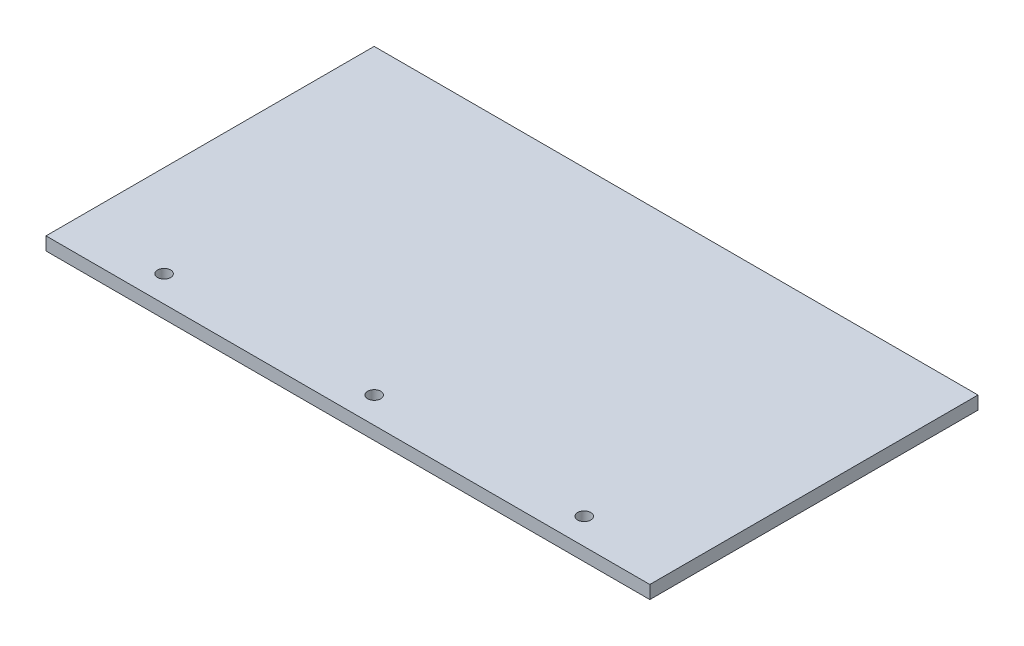
SolidWorks part; units mm, degrees
ref_plane "Front Plane" through (0, 0, 0) normal (0, 0, 1) x (1, 0, 0)
ref_plane "Top Plane" through (0, 0, 0) normal (0, 1, 0) x (1, 0, 0)
ref_plane "Right Plane" through (0, 0, 0) normal (1, 0, 0) x (0, 0, -1)
sketch "Sketch1" plane through (0, 0, 0) normal (0, 1, 0) x (1, 0, 0)
  line L1 (0, 0) -> (292.1, 0)
  line L2 (0, 0) -> (0, 158.75)
  line L3 (0, 158.75) -> (292.1, 158.75)
  line L4 (292.1, 0) -> (292.1, 158.75)
  dimension "D1" = 292.1
  dimension "D2" = 158.75
extrude "Boss-Extrude1" add sketch "Sketch1" along normal blind 6.35
sketch "Sketch2" plane through (0, 6.35, 0) normal (0, 1, 0) x (1, 0, 0)
  line L0 (0, 25.4) -> (292.1, 25.4) construction
  line L1 (0, 12.7) -> (292.1, 12.7) construction
  line L3 (146.05, 25.4) -> (146.05, 158.75) construction
  line L4 (0, 158.75) -> (0, 0)
  line L5 (0, 0) -> (292.1, 0)
  line L6 (292.1, 0) -> (292.1, 158.75)
  line L7 (292.1, 158.75) -> (0, 158.75)
  line L8 (0, 158.75) -> (0, 0) construction
  line L9 (0, 0) -> (292.1, 0) construction
  line L10 (292.1, 0) -> (292.1, 158.75) construction
  line L11 (292.1, 158.75) -> (0, 158.75) construction
  line L12 (292.1, 92.075) -> (0, 92.075) construction
  circle A0 centre (146.05, 12.7) radius 3.175
  circle A1 centre (247.65, 12.7) radius 3.175
  circle A2 centre (44.45, 12.7) radius 3.175
  point P8 (146.05, 92.075)
  dimension "D6" = 6.35
  dimension "D7" = 6.35
  dimension "D8" = 6.35
  dimension "D2" = 25.4
  dimension "D3" = 12.7
  dimension "D4" = 101.6
  dimension "D5" = 101.6
  dimension "D1" = 0
extrude "Cut-Extrude2" cut sketch "Sketch2" against normal blind 6.35
ref_plane "Plane2" through (0, 0, -79.375) normal (0, 0, 1) x (1, 0, 0)
ref_plane "Plane3" through (146.05, 0, 0) normal (-1, 0, 0) x (0, 0, 1)
ref_plane "Plane4" through (0, 0, -92.075) normal (0, 0, -1) x (-1, 0, 0)
equation "\"D5@Sketch2\"=\"D4@Sketch2\""
equation "\"D7@Sketch2\"=\"D6@Sketch2\""
equation "\"D8@Sketch2\"=\"D7@Sketch2\""
